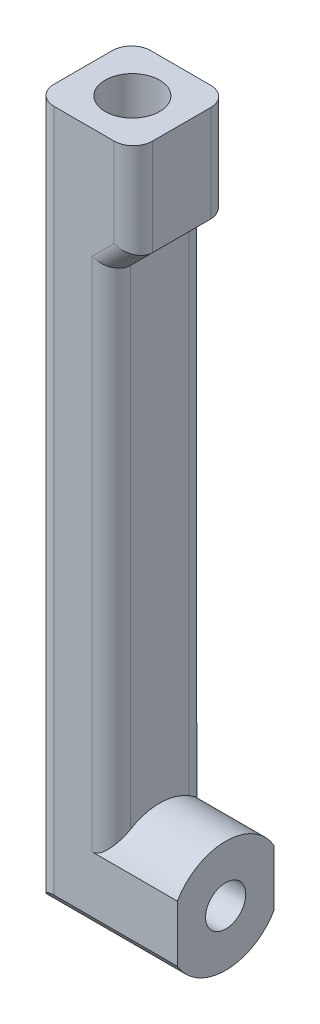
SolidWorks part; units mm, degrees
note: The reader was unsure of these and kept them because the rebuilt part matched: shared geometry of "Sketch4<3>".
ref_plane "Front Plane" through (0, 0, 0) normal (0, 0, 1) x (1, 0, 0)
ref_plane "Top Plane" through (0, 0, 0) normal (0, 1, 0) x (1, 0, 0)
ref_plane "Right Plane" through (0, 0, 0) normal (1, 0, 0) x (0, 0, -1)
sketch "Sketch1" plane through (0, 0, 0) normal (0, 0, 1) x (1, 0, 0)
  line L0 (-93.5, 49.4827) -> (-108.4, 49.4827)
  line L1 (-111.9, 123.7896) -> (-89.3537, 123.7896) construction
  line L2 (-108.4, 49.4827) -> (-108.4, 123.7896)
  line L3 (-83.5, 61.1827) -> (-93.5, 61.1827) construction
  line L4 (-108.4, 123.7896) -> (-98.1, 123.7896)
  line L5 (-98.1, 123.7896) -> (-98.1, 113.6896)
  line L8 (-93.5, 49.4827) -> (-83.5, 49.4827) construction
  line L9 (-98.1, 113.6896) -> (-100.4, 113.6896)
  line L10 (-106.1, 123.7896) -> (-100.4, 123.7896) construction
  line L11 (-106.1, 123.7896) -> (-106.1, 115.6896) construction
  line L12 (-106.1, 115.6896) -> (-100.4, 115.6896) construction
  line L13 (-100.4, 123.7896) -> (-100.4, 115.6896) construction
  line L14 (-100.4, 113.6896) -> (-100.4, 61.1827)
  line L17 (-111.9, 123.7896) -> (-89.3537, 123.7896) construction
  line L23 (-84.5, 58.1827) -> (-84.5, 52.4827) construction
  line L24 (-98.9, 142.7896) -> (-98.9, 127.7896) construction
  line L27 (-100.4, 61.1827) -> (-93.5, 61.1827)
  line L28 (-93.5, 61.1827) -> (-93.5, 49.4827)
  point P11 (-103.25, 123.7896)
  point P24 (-103.25, 123.7896)
  dimension "D1" = 5.7
  dimension "D4" = 8.1
  dimension "D5" = 2
  dimension "D2" = 2.3
  dimension "D3" = 8
  dimension "D6" = 1.5
extrude "Boss-Extrude1" add sketch "Sketch1" along normal mid plane 10.1
sketch "Sketch2" plane through (-108.4, 0, 0) normal (-1, 0, 0) x (0, 0, 1)
  circle A0 centre (0, 55.3327) radius 2.1
  circle A1 centre (0, 55.3327) radius 2.85 construction
  dimension "D1" = 4.2
extrude "Cut-Extrude1" cut sketch "Sketch2" against normal through all
sketch "Sketch3" plane through (0, 123.7896, 0) normal (0, 1, 0) x (1, 0, 0)
  line L0 (-98.1, 5.05) -> (-108.4, 5.05) construction
  line L1 (-98.1, -5.05) -> (-98.1, 5.05) construction
  circle A0 centre (-103.25, 0) radius 2.85
  point P4 (-103.25, 5.05)
  point P8 (-98.1, 0)
  dimension "D1" = 5.7
extrude "Cut-Extrude2" cut sketch "Sketch3" against normal blind 9.5
sketch "Sketch5" plane through (0, 0, 5.05) normal (0, 0, 1) x (1, 0, 0)
  line L0 (-98.1, 113.6896) -> (-100.4, 111.3896)
  line L1 (-100.4, 61.1827) -> (-100.4, 113.6896) construction
  line L2 (-100.4, 111.3896) -> (-100.4, 113.6896)
  line L3 (-100.4, 113.6896) -> (-98.1, 113.6896)
extrude "Boss-Extrude2" add sketch "Sketch5" against normal up to surface (10.1 mm away) up to face at (-100.1, 87.0361, -5.05)
sketch "Sketch4" plane through (-108.4, 0, 0) normal (-1, 0, 0) x (0, 0, 1)
  line L0 (-5.05, 49.4827) -> (5.05, 49.4827)
  line L1 (5.05, 49.4827) -> (5.05, 52.3798)
  line L2 (5.05, 123.7896) -> (5.05, 49.4827) construction
  line L3 (-5.05, 52.3798) -> (-5.05, 49.4827)
  line L4 (-5.05, 123.7896) -> (-5.05, 49.4827) construction
  line L5 (-5.05, 52.3798) -> (-5.05, 61.1827)
  line L6 (-5.05, 61.1827) -> (5.05, 61.1827)
  line L7 (5.05, 61.1827) -> (5.05, 52.3798)
  circle A0 centre (0, 55.3327) radius 5.85 construction
  arc A2 (-5.05, 52.3798) -> (5.05, 52.3798) centre (0, 55.3327) ccw
  arc A3 (5.05, 52.3798) -> (-5.05, 52.3798) centre (0, 55.3327) ccw
  line M3 (-5.05, 123.7896) -> (-5.05, 49.4827)
  line M5 (5.05, 49.4827) -> (5.05, 123.7896)
extrude "Cut-Extrude3" cut sketch "Sketch4" against normal through all
extrude "Cut-Extrude4" cut sketch "Sketch4<3>" along normal up to surface (6.9 mm away) from surface contours A3 L6 M3 | A3 L6 M5
sketch "Sketch4<3>" plane through (-108.4, 0, 0) normal (-1, 0, 0) x (0, 0, 1) same geometry as "Sketch4"
fillet "Fillet1" radius 2 8 edges at (-100.4, 84.8376, 5.05) (-108.4, 88.0847, -5.05) (-98.1, 118.7396, -5.05) (-108.4, 88.0847, 5.05) (-98.1, 118.7396, 5.05) (-100.4, 84.8376, -5.05) (-99.25, 112.5396, -5.05) (-99.25, 112.5396, 5.05)
equation "\"width\"= 24"
equation "\"thk\"= 3"
equation "\"holesize\"= 4.2"
equation "\"holedistance\"= ( 20 + 12 ) / 2"
equation "\"threaded_hole\"= 3.9"
equation "\"fillet_radius\"= 2"
equation "\"ground_clearance\"= 25"
equation "\"tire_thk\"= 3"
equation "\"innerwheel_diam\" = \"wheel_diam\"-2*\"tire_thk\""
equation "\"innerwheel_thk\"= 8"
equation "\"wheel_diam\"= 2*(\"width\"/2+\"ground_clearance\")"
equation "\"coloursensor_holesize\"= 2.65"
equation "\"hole_to_edge\" = 4"
equation "\"M4_insert_diam\"= 5.7"
equation "\"D1@Sketch1\"=\"M4_insert_diam\""
equation "\"D1@Boss-Extrude1\"=\"M4_insert_diam\"+2*2.2"
equation "\"D1@Sketch2\"=\"holesize\""
equation "\"D1@Sketch3\"=\"M4_insert_diam\""
